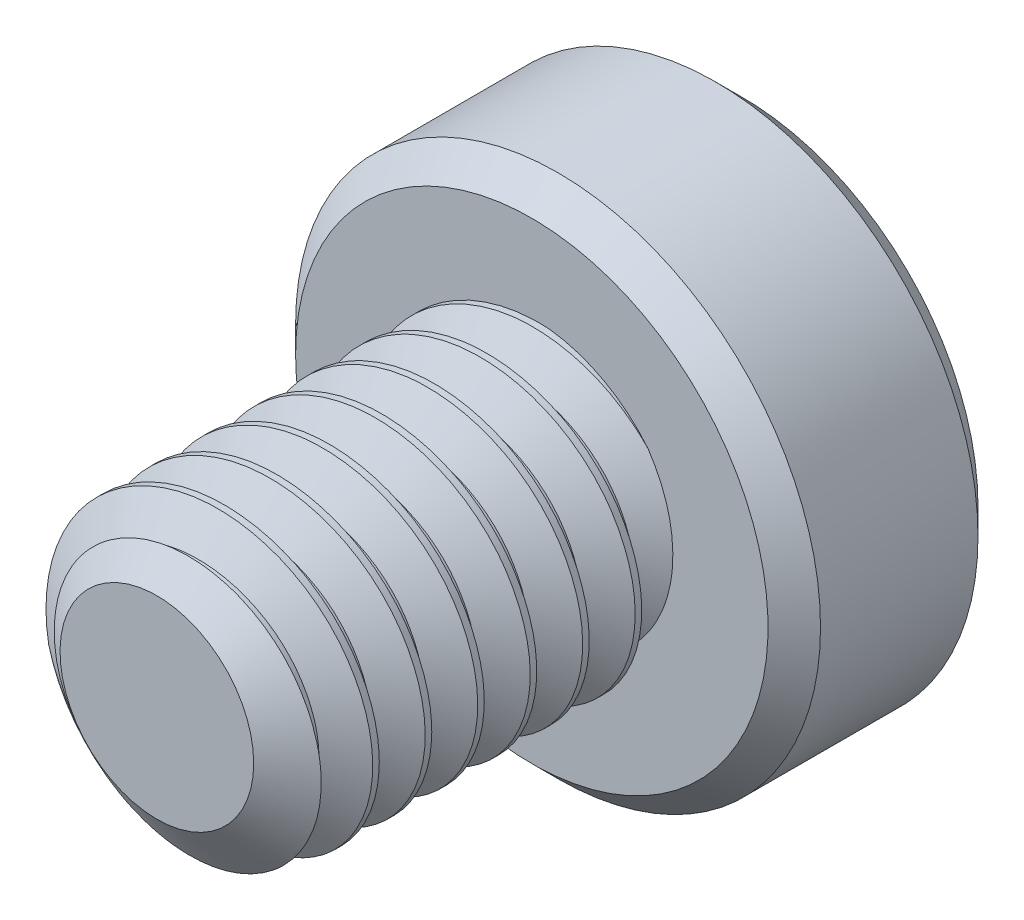
SolidWorks part; units mm, degrees
other "DetailItem1"
ref_plane "Front Plane" through (0, 0, 0) normal (0, 0, 1) x (1, 0, 0)
ref_plane "Top Plane" through (0, 0, 0) normal (0, 1, 0) x (1, 0, 0)
ref_plane "Right Plane" through (0, 0, 0) normal (1, 0, 0) x (0, 0, -1)
sketch "Sketch1" plane through (0, 0, 0) normal (0, 0, 1) x (1, 0, 0)
  circle A0 centre (0, 0) radius 2
  dimension "OD" = 4
extrude "Extrude1" add sketch "Sketch1" against normal blind 5
sketch "Sketch2" plane through (0, 0, 0) normal (0, 0, 1) x (1, 0, 0)
  circle A0 centre (0, 0) radius 2 construction
  circle A1 centre (0, 0) radius 2
curve "Helix/Spiral1" pitch 0.7 height 5.7 radius 2 centre (0, 0, 0) axis (0, 0, -1) start towards (0, 1, 0) parameters "pitch"=0.7
sketch "Sketch3" plane through (0, 0, 0) normal (1, 0, 0) x (0, 0, -1)
  line L0 (-0.6125, 2) -> (-0.35, 1.5453)
  line L1 (-0.35, 1.5453) -> (-0.2625, 1.5453)
  line L2 (-0.2625, 1.5453) -> (0, 2)
  line L3 (-0.6125, 2) -> (0, 2)
  line L4 (-0.3062, 2) -> (-0.3063, 1.5453) construction
  line L5 (-0.4813, 1.7727) -> (-0.1313, 1.7727) construction
  line L6 (0, 2) -> (0, -2) construction
  dimension "D1" = 0.0875
  dimension "D2" = 0.35
  dimension "D3" = 60
sweep "Cut-Sweep1" cut profiles "Sketch3" path "Helix/Spiral1"
sketch "Sketch4" plane through (0, 0, 0) normal (1, 0, 0) x (0, 0, -1)
  line L0 (0.4962, 2) -> (0, 1.2913)
  line L1 (0, 1.2913) -> (0, 2)
  line L2 (0.4962, 2) -> (0, 2)
  line L3 (-0.6125, 2) -> (0, 2) construction
  line L4 (0, 0) -> (7.0209, 0) construction
  dimension "D1" = 55
  dimension "D2" = 0.254
revolve "Cut-Revolve1" cut sketch "Sketch4" angle 360 about L4
sketch "Sketch6" plane through (0, 0, -5) normal (0, 0, -1) x (-1, 0, 0)
  circle A0 centre (0, 0) radius 3.5
  dimension "head dia" = 7
extrude "Extrude2" add sketch "Sketch6" along normal blind 2.8
sketch "Sketch7" plane through (0, 0, -7.8) normal (0, 0, -1) x (-1, 0, 0)
  line L1 (0, 1.4434) -> (-1.25, 0.7217)
  line L2 (-1.25, 0.7217) -> (-1.25, -0.7217)
  line L3 (-1.25, -0.7217) -> (0, -1.4434)
  line L4 (0, -1.4434) -> (1.25, -0.7217)
  line L5 (1.25, -0.7217) -> (1.25, 0.7217)
  line L6 (1.25, 0.7217) -> (0, 1.4434)
  circle A0 centre (0, 0) radius 1.25 construction
  dimension "hex dia" = 2.5
extrude "Cut-Extrude1" cut sketch "Sketch7" against normal blind 1.875
sketch "Sketch8" plane through (0, 0, -7.8) normal (0, 0, -1) x (-1, 0, 0)
  circle A0 centre (0, 0) radius 1.4434
extrude "Cut-Extrude2" cut sketch "Sketch8" against normal through all draft 45
chamfer "Chamfer1" distance 0.35 angle 45 2 edges at (-3.5, 0, -7.8) (-3.5, 0, -5)
sketch "Sketch10" plane through (0, 0, -5) normal (0, 0, 1) x (1, 0, 0)
  circle A1 centre (0, 0) radius 2
  circle A2 centre (0, 0) radius 2
  dimension "D1" = 0
ref_plane "Plane1" through (0, 0, -30) normal (0, 0, 1) x (1, 0, 0)
extrude "partial thread" [suppressed] add sketch "Sketch10" along normal up to surface (20 mm away) separate body up to plane "Plane1"
chamfer "Chamfer2" [suppressed] distance 0.08 angle 45
combine bodies "Combine1" [suppressed] operation type add bodies to combine 107 108
sketch "Sketch9" plane through (0, 0, 0) normal (1, 0, 0) x (0, 0, -1)
  line L0 (0, 2) -> (0, -2) construction
  line L1 (1.75, 2) -> (1.75, -2) construction
  dimension "D1" = 1.75
equation "\"D3@Helix/Spiral1\" = \"screw length@Extrude1\"+\"pitch@Helix/Spiral1\""
equation "\"D1@Sketch3\" = \"pitch@Helix/Spiral1\"*.125"
equation "\"D2@Sketch3\" = \"pitch@Helix/Spiral1\"*.5"
equation "\"D1@Cut-Extrude1\" = \"hex dia@Sketch7\"*.75"
equation "\"D1@Chamfer1\" = \"head dia@Sketch6\"*.05"
equation "\"D1@Sketch9\" = \"pitch@Helix/Spiral1\"*2.5"
equation "\"D1@Chamfer2\"=\"OD@Sketch1\"*.02"
